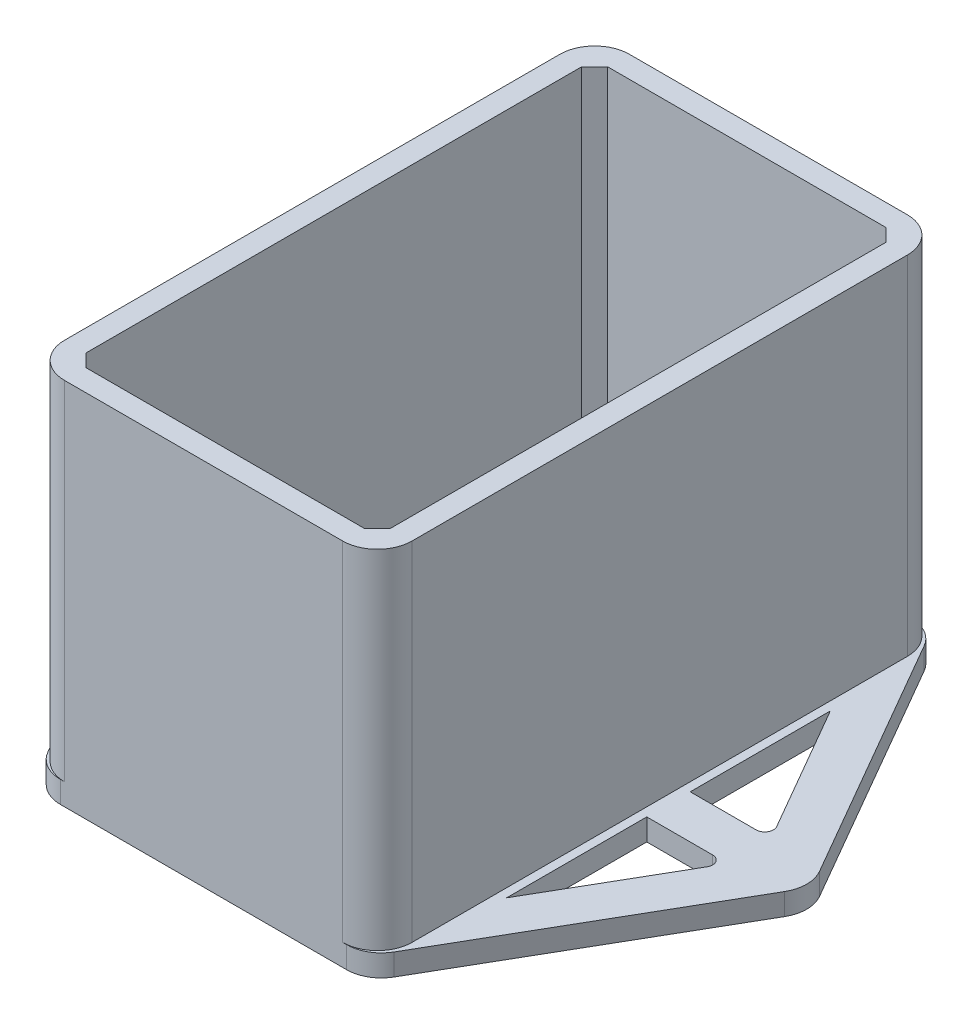
SolidWorks part; units mm, degrees
ref_plane "Front Plane" through (0, 0, 0) normal (0, 0, 1) x (1, 0, 0)
ref_plane "Top Plane" through (0, 0, 0) normal (0, 1, 0) x (1, 0, 0)
ref_plane "Right Plane" through (0, 0, 0) normal (1, 0, 0) x (0, 0, -1)
sketch "Sketch1" plane through (0, 0, 0) normal (0, 1, 0) x (1, 0, 0)
  line L1 (-75.0555, 0) -> (-37.5278, -65)
  line L2 (-37.5278, -65) -> (37.5278, -65)
  line L3 (37.5278, -65) -> (75.0555, 0)
  line L4 (75.0555, 0) -> (37.5278, 65)
  line L5 (37.5278, 65) -> (-37.5278, 65)
  line L6 (-37.5278, 65) -> (-75.0555, 0)
  circle A0 centre (0, 0) radius 65 construction
  circle A1 centre (0, 0) radius 50 construction
  dimension "D2" = 100
  dimension "D1" = 130
extrude "Boss-Extrude1" add sketch "Sketch1" along normal blind 5
fillet "Fillet1" radius 8 6 edges at (37.5278, 2.5, -65) (75.0555, 2.5, 0) (37.5278, 2.5, 65) (-37.5278, 2.5, 65) (-75.0555, 2.5, 0) (-37.5278, 2.5, -65)
sketch "Sketch3" plane through (0, 5, 0) normal (0, 1, 0) x (1, 0, 0)
  line L0 (-32.909, -65) -> (32.909, -65) construction
  line L1 (-32, 65) -> (32, 65)
  line L2 (-40, 57) -> (-40, -57)
  line L3 (-32, -65) -> (32, -65)
  line L4 (40, 57) -> (40, -57)
  line L5 (-40, 65) -> (40, -65) construction
  line L6 (-40, -65) -> (40, 65) construction
  arc A0 (40, 57) -> (32, 65) centre (32, 57) ccw
  arc A1 (40, -57) -> (32, -65) centre (32, -57) cw
  arc A2 (-32, -65) -> (-40, -57) centre (-32, -57) cw
  arc A3 (-32, 65) -> (-40, 57) centre (-32, 57) ccw
  point P0 (0, 0)
  dimension "D1" = 8
  dimension "D2" = 64
extrude "Boss-Extrude2" add sketch "Sketch3" along normal blind 80
sketch "Sketch4" plane through (0, 85, 0) normal (0, 1, 0) x (1, 0, 0)
  line L0 (-35, 57) -> (-32, 60)
  line L1 (32, 60) -> (35, 57)
  line L2 (35, -57) -> (32, -60)
  line L3 (-35, -57) -> (-32, -60)
  line L9 (-32, -60) -> (32, -60)
  line L10 (35, -57) -> (35, 57)
  line L11 (32, 60) -> (-32, 60)
  line L12 (-35, 57) -> (-35, -57)
  line L13 (-32, -60) -> (32, -60)
  line L14 (35, -57) -> (35, 57)
  line L15 (32, 60) -> (-32, 60)
  line L16 (-35, 57) -> (-35, -57)
  arc A9 (-35, -57) -> (-32, -60) centre (-32, -57) ccw
  arc A10 (32, -60) -> (35, -57) centre (32, -57) ccw
  arc A11 (35, 57) -> (32, 60) centre (32, 57) ccw
  arc A12 (-32, 60) -> (-35, 57) centre (-32, 57) ccw
  dimension "D1" = 5
extrude "Cut-Extrude1" cut sketch "Sketch4" against normal up to surface (85 mm away) up to face at (0, 0, 0)
sketch "Sketch8" plane through (0, 0, 0) normal (0, 1, 0) x (1, 0, 0)
  line L0 (0, 40) -> (0, 25) construction
  line L1 (0, 55) -> (0, 65) construction
  line L2 (9.5263, 26.5) -> (24.2487, 52) construction
  line L3 (22.5167, 55) -> (-22.5167, 55) construction
  line L4 (-24.2487, 52) -> (-9.5263, 26.5) construction
  line L5 (-12.5, 0) -> (-62.3346, 0) construction
  line L36 (6.9282, 25) -> (-6.9282, 25) construction
  line L37 (27.7128, 5) -> (57.1577, 5) construction
  line L38 (58.8897, 8) -> (36.3731, 47) construction
  line L39 (32.909, 47) -> (18.1865, 21.5) construction
  line L40 (25.1147, 6.5) -> (18.1865, 18.5) construction
  line L41 (18.1865, -21.5) -> (32.909, -47) construction
  line L42 (36.3731, -47) -> (58.8897, -8) construction
  line L43 (57.1577, -5) -> (27.7128, -5) construction
  line L44 (18.1865, -18.5) -> (25.1147, -6.5) construction
  line L45 (-9.5263, -26.5) -> (-24.2487, -52) construction
  line L46 (-22.5167, -55) -> (22.5167, -55) construction
  line L47 (24.2487, -52) -> (9.5263, -26.5) construction
  line L48 (-6.9282, -25) -> (6.9282, -25) construction
  line L49 (-27.7128, -5) -> (-57.1577, -5) construction
  line L50 (-58.8897, -8) -> (-36.3731, -47) construction
  line L51 (-32.909, -47) -> (-18.1865, -21.5) construction
  line L52 (-25.1147, -6.5) -> (-18.1865, -18.5) construction
  line L53 (-18.1865, 21.5) -> (-32.909, 47) construction
  line L54 (-42, 37.2539) -> (-58.8897, 8)
  line L55 (-57.1577, 5) -> (-42, 5)
  line L56 (-18.1865, 18.5) -> (-25.1147, 6.5) construction
  line L57 (-42, 5) -> (-42, 37.2539)
  line L58 (-40, 57) -> (-40, -57) construction
  line L59 (-40, 57) -> (-40, -57) construction
  line L60 (-36.3731, 47) -> (-42, 37.2539) construction
  line L61 (-42, 5) -> (-27.7128, 5) construction
  line L62 (-42, -5) -> (-42, -37.2539)
  line L63 (-57.1577, -5) -> (-42, -5)
  line L64 (-42, -37.2539) -> (-58.8897, -8)
  line L65 (42, -37.2539) -> (58.8897, -8)
  line L66 (57.1577, -5) -> (42, -5)
  line L67 (42, -5) -> (42, -37.2539)
  line L68 (42, 5) -> (42, 37.2539)
  line L69 (57.1577, 5) -> (42, 5)
  line L70 (42, 37.2539) -> (58.8897, 8)
  circle A0 centre (0, 0) radius 12.5 construction
  circle A1 centre (0, 40) radius 15 construction
  arc A3 (-22.5167, 55) -> (-24.2487, 52) centre (-22.5167, 53) ccw
  arc A4 (24.2487, 52) -> (22.5167, 55) centre (22.5167, 53) ccw construction
  arc A5 (6.9282, 25) -> (9.5263, 26.5) centre (6.9282, 28) ccw construction
  arc A6 (-6.9282, 25) -> (-9.5263, 26.5) centre (-6.9282, 28) cw construction
  arc A7 (25.1147, 6.5) -> (27.7128, 5) centre (27.7128, 8) ccw construction
  arc A8 (57.1577, 5) -> (58.8897, 8) centre (57.1577, 7) ccw construction
  arc A9 (36.3731, 47) -> (32.909, 47) centre (34.641, 46) ccw construction
  arc A10 (18.1865, 18.5) -> (18.1865, 21.5) centre (20.7846, 20) cw construction
  arc A11 (18.1865, -18.5) -> (18.1865, -21.5) centre (20.7846, -20) ccw construction
  arc A12 (32.909, -47) -> (36.3731, -47) centre (34.641, -46) ccw construction
  arc A13 (58.8897, -8) -> (57.1577, -5) centre (57.1577, -7) ccw construction
  arc A14 (25.1147, -6.5) -> (27.7128, -5) centre (27.7128, -8) cw construction
  arc A15 (-6.9282, -25) -> (-9.5263, -26.5) centre (-6.9282, -28) ccw construction
  arc A16 (-24.2487, -52) -> (-22.5167, -55) centre (-22.5167, -53) ccw construction
  arc A17 (22.5167, -55) -> (24.2487, -52) centre (22.5167, -53) ccw construction
  arc A18 (6.9282, -25) -> (9.5263, -26.5) centre (6.9282, -28) cw construction
  arc A19 (-25.1147, -6.5) -> (-27.7128, -5) centre (-27.7128, -8) ccw construction
  arc A20 (-57.1577, -5) -> (-58.8897, -8) centre (-57.1577, -7) ccw construction
  arc A21 (-36.3731, -47) -> (-32.909, -47) centre (-34.641, -46) ccw construction
  arc A22 (-18.1865, -18.5) -> (-18.1865, -21.5) centre (-20.7846, -20) cw construction
  arc A23 (-18.1865, 18.5) -> (-18.1865, 21.5) centre (-20.7846, 20) ccw construction
  arc A24 (-32.909, 47) -> (-36.3731, 47) centre (-34.641, 46) ccw construction
  arc A25 (-58.8897, 8) -> (-57.1577, 5) centre (-57.1577, 7) ccw
  arc A26 (-25.1147, 6.5) -> (-27.7128, 5) centre (-27.7128, 8) cw construction
  arc A27 (-58.8897, -8) -> (-57.1577, -5) centre (-57.1577, -7) cw
  arc A28 (57.1577, -5) -> (58.8897, -8) centre (57.1577, -7) cw construction
  arc A29 (58.8897, -8) -> (57.1577, -5) centre (57.1577, -7) ccw
  arc A30 (58.8897, 8) -> (57.1577, 5) centre (57.1577, 7) cw
  point P19 (0, 25)
  point P30 (0, 0)
  point P66 (0, 0)
  point P88 (0, 0)
  dimension "D1" = 25
  dimension "D3" = 30
  dimension "D6" = 2
  dimension "D8" = 3
  dimension "D2" = 40
  dimension "D4" = 10
  dimension "D5" = 15
  dimension "D7" = 25
  dimension "D9" = 2
  dimension "D10" = 6
extrude "Cut-Extrude2" cut sketch "Sketch8" along normal up to surface (5 mm away) contours A30 L70 L68 L69 | L65 A29 L66 L67 | A27 L64 L62 L63 | L54 A25 L55 L57 region at (-48.1047, 0, -15.8435) region at (-48.1047, 0, 15.8435) region at (48.1047, 0, 15.8435) region at (48.1047, 0, -15.8435) up to face at (-44.0442, 5, 0)
